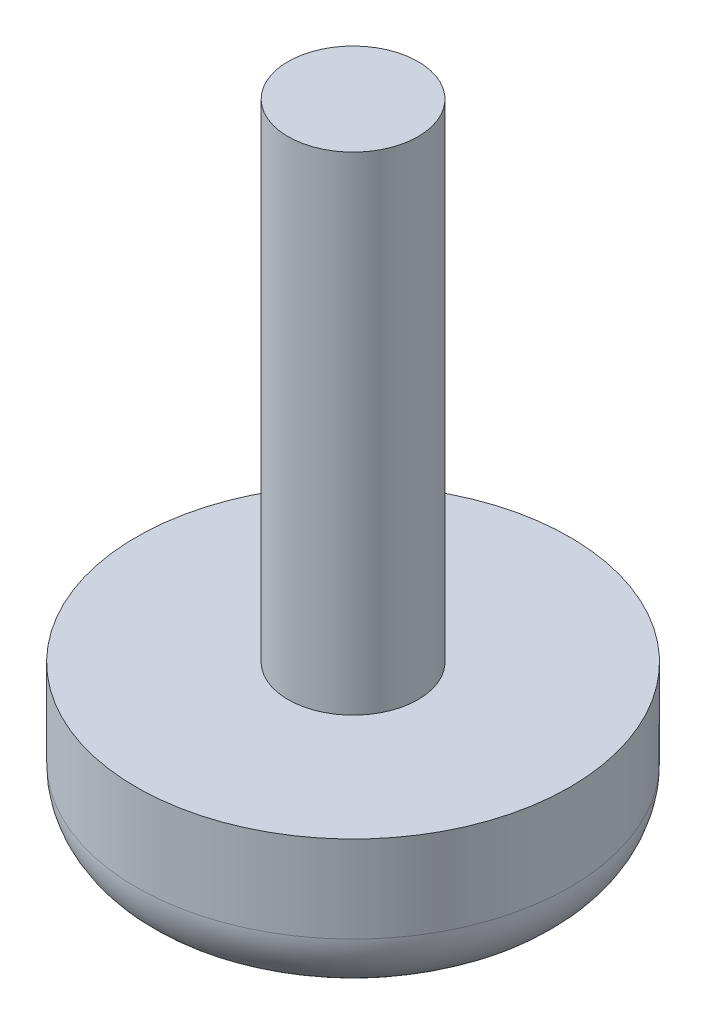
SolidWorks part; units mm, degrees
ref_plane "Plan de face" through (0, 0, 0) normal (0, 0, 1) x (1, 0, 0)
ref_plane "Plan de dessus" through (0, 0, 0) normal (0, 1, 0) x (1, 0, 0)
ref_plane "Plan de droite" through (0, 0, 0) normal (1, 0, 0) x (0, 0, -1)
sketch "Esquisse1" plane through (0, 0, 0) normal (0, 0, 1) x (1, 0, 0)
  line L1 (0, 0) -> (-3, 0)
  line L2 (0, 0) -> (0, 22.5)
  line L3 (0, 22.5) -> (-3, 22.5)
  line L4 (-3, 0) -> (-3, 22.5)
  line L5 (0, 0) -> (-10, 0)
  line L6 (0, 0) -> (0, -7)
  line L7 (0, -7) -> (-10, -7)
  line L8 (-10, 0) -> (-10, -7)
  dimension "D1" = 3
  dimension "D2" = 7
  dimension "D3" = 22.5
  dimension "D4" = 10
revolve "Révolution1" add sketch "Esquisse1" angle 360 about L2 region at (-5, -3.5, 0)
fillet "Congé1" radius 3 1 edges at (10, -7, 0)
